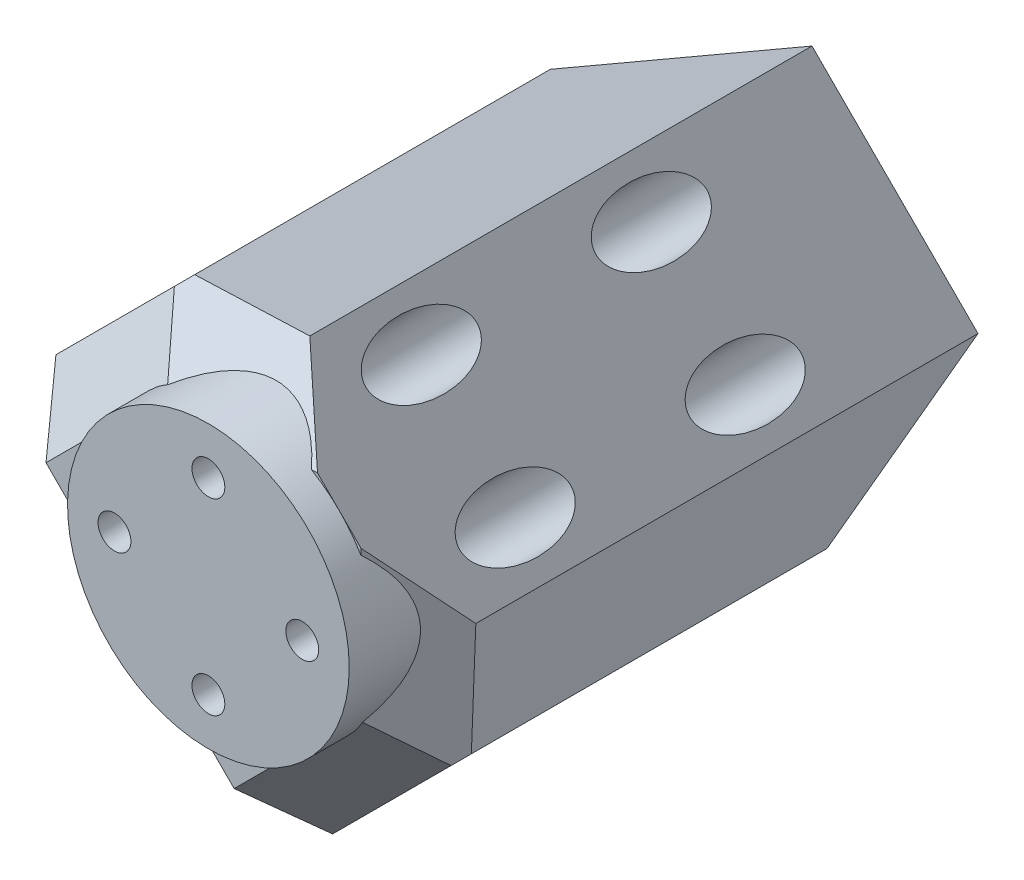
SolidWorks part; units mm, degrees
ref_plane "Front Plane" through (0, 0, 0) normal (0, 0, 1) x (1, 0, 0)
ref_plane "Top Plane" through (0, 0, 0) normal (0, 1, 0) x (1, 0, 0)
ref_plane "Right Plane" through (0, 0, 0) normal (1, 0, 0) x (0, 0, -1)
sketch "Sketch1" plane through (0, 0, 0) normal (0, 0, 1) x (1, 0, 0)
  circle A0 centre (0, 0) radius 9
  circle A1 centre (0, 0) radius 6
  circle A2 centre (0, 6) radius 1.05
  circle A3 centre (-6, 0) radius 1.05
  circle A4 centre (0, -6) radius 1.05
  circle A5 centre (6, 0) radius 1.05
  dimension "D1" = 18
  dimension "D2" = 12
  dimension "D3" = 2.1
extrude "Boss-Extrude1" add sketch "Sketch1" along normal blind 2 contours A0 A5 A1 A4 A3 A2 | A5 A1 A2 A3 A4 region at (-8.7454, 0, 0) region at (0, 0, 0)
ref_plane "Plane1" through (0, 0, -50) normal (0, 0, -1) x (-1, 0, 0)
sketch "Sketch2" plane through (0, 0, 0) normal (0, 0, -1) x (-1, 0, 0)
  line L0 (0, 0) -> (9, 0)
  line L1 (-15.2028, -2.4749) -> (2.4749, 15.2028)
  line L2 (-15.2028, -2.4749) -> (-2.4749, -15.2028)
  line L3 (2.4749, 15.2028) -> (15.2028, 2.4749)
  line L4 (-2.4749, -15.2028) -> (15.2028, 2.4749)
  line L5 (-15.2028, -2.4749) -> (15.2028, 2.4749) construction
  line L6 (2.4749, 15.2028) -> (-2.4749, -15.2028) construction
  circle A0 centre (0, 0) radius 9 construction
  dimension "D1" = 45
  dimension "D2" = 25
  dimension "D3" = 18
sketch "Sketch3" plane through (0, 0, -50) normal (0, 0, -1) x (-1, 0, 0)
  line L0 (0, 0) -> (10.6066, -10.6066)
  line L1 (-15.2028, -2.4749) -> (15.2028, 2.4749) construction
  line L2 (-0.7071, -16.9706) -> (16.9706, 0.7071)
  line L3 (-0.7071, -16.9706) -> (4.2426, -21.9203)
  line L4 (16.9706, 0.7071) -> (21.9203, -4.2426)
  line L5 (4.2426, -21.9203) -> (21.9203, -4.2426)
  line L6 (-0.7071, -16.9706) -> (21.9203, -4.2426) construction
  line L7 (16.9706, 0.7071) -> (4.2426, -21.9203) construction
  dimension "D1" = 15
  dimension "D2" = 90
  dimension "D3" = 7
  dimension "D4" = 25
loft "Loft1" add section "Sketch3" section "Sketch2" connector at (0.7071, -16.9706, -50) connector at (15.2028, -2.4749, 0)
chamfer "Chamfer1" distance 4 angle 45 2 edges
sketch "Sketch5" plane through (0, 0, 2) normal (0, 0, 1) x (1, 0, 0)
  circle A20 centre (-6, 0) radius 2.05
  circle A21 centre (-6, 0) radius 2.05
  circle A23 centre (0, -6) radius 2.05
  circle A24 centre (0, -6) radius 2.05
  circle A26 centre (0, 6) radius 2.05
  circle A27 centre (0, 6) radius 2.05
  circle A29 centre (6, 0) radius 2.05
  circle A30 centre (6, 0) radius 2.05
  dimension "D1" = 1
  dimension "D2" = 1
  dimension "D3" = 1
  dimension "D4" = 1
sketch "Sketch6" plane through (0, 0, 2) normal (0, 0, 1) x (1, 0, 0)
  circle A0 centre (0, -6) radius 1.05 construction
  circle A1 centre (0, 0) radius 9
  circle A2 centre (0, 0) radius 9
  circle A3 centre (6, 0) radius 1.05 construction
  circle A4 centre (0, 6) radius 1.05 construction
  circle A5 centre (-6, 0) radius 1.05 construction
  circle A6 centre (0, -6) radius 1.05
  circle A7 centre (6, 0) radius 1.05
  circle A8 centre (0, 6) radius 1.05
  circle A9 centre (-6, 0) radius 1.05
  dimension "D1" = 0
extrude "Cut-Extrude3" cut sketch "Sketch6" against normal blind 53 contours A9 | A8 | A7 | A6
extrude "Cut-Extrude4" cut sketch "Sketch5" against normal blind 53 from surface starting at face at (10.2382, -1.7826, 0)
chamfer "Chamfer2" distance 5 angle 45 2 edges
chamfer "Chamfer3" distance 5 angle 45 2 edges at (11.6387, 0.325, 0)
sketch "Sketch8" plane through (-8.8388, 8.8388, 0) normal (-0.7071, 0.7071, 0) x (0, 0, 1)
  line L1 (-50, -11.5) -> (-9.3546, -11.5)
  line L2 (-50, -11.5) -> (-50, -33.28)
  line L3 (-50, -33.28) -> (-9.3546, -33.28)
  line L4 (-9.3546, -11.5) -> (-9.3546, -33.28)
extrude "Cut-Extrude5" cut sketch "Sketch8" against normal blind 34
